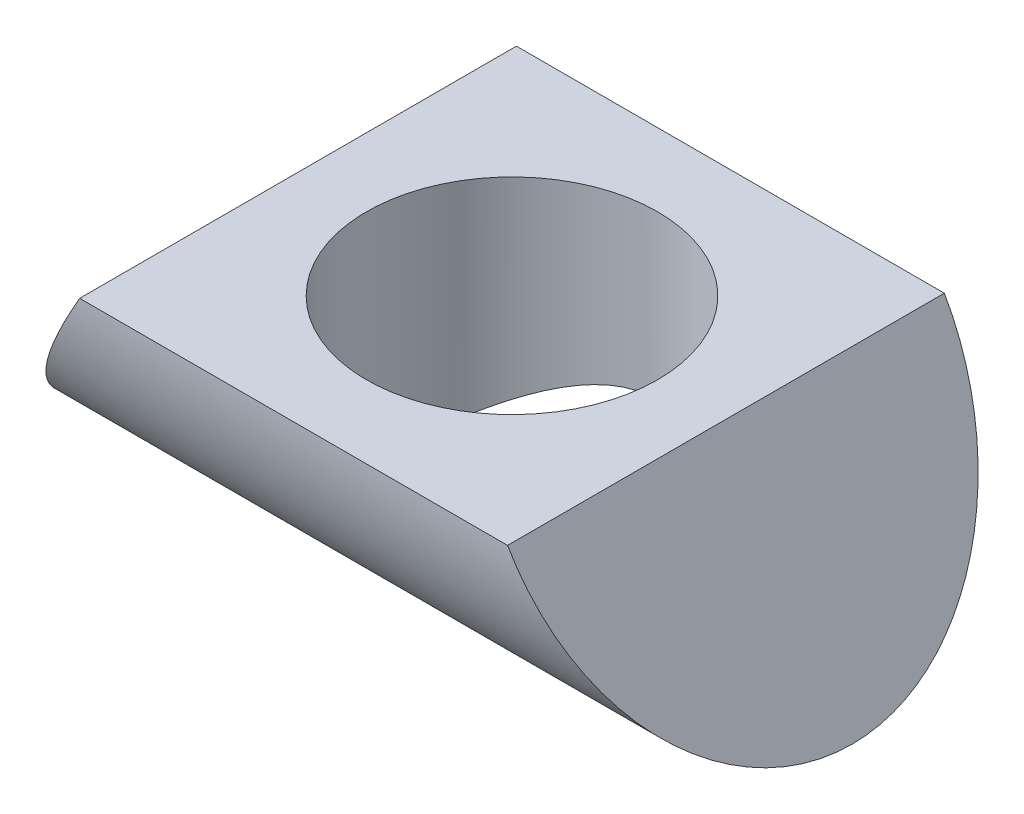
SolidWorks part; units mm, degrees
material "6061-T6 (SS)"
ref_plane "Front Plane" through (0, 0, 0) normal (0, 0, 1) x (1, 0, 0)
ref_plane "Top Plane" through (0, 0, 0) normal (0, 1, 0) x (1, 0, 0)
ref_plane "Right Plane" through (0, 0, 0) normal (1, 0, 0) x (0, 0, -1)
sketch "Sketch1" plane through (0, 0, 0) normal (0, 1, 0) x (1, 0, 0)
  line L0 (0, 20.354) -> (0, -20.728) construction
  line L1 (-20, 8) -> (20, 8) construction
  line L2 (-20, -8) -> (20, -8) construction
  circle A0 centre (-20, 0) radius 4.7625
  arc A1 (-20, 8) -> (-20, -8) centre (-20, 0) ccw construction
  circle A2 centre (20, 0) radius 4.7625
  arc A3 (20, 8) -> (20, -8) centre (20, 0) cw construction
  dimension "D1" = 9.525
  dimension "D2" = 20
  dimension "D3" = 16
sketch "Sketch2" plane through (0, 0, 0) normal (1, 0, 0) x (0, 0, -1)
  line L0 (-7.145, 0) -> (7.145, 0)
  arc A0 (-7.145, 0) -> (7.145, 0) centre (0, 0) ccw
  dimension "D1" = 14.29
extrude "Boss-Extrude3" add sketch "Sketch2" along normal blind 34 and the other way blind 34
extrude "Cut-Extrude1" cut sketch "Sketch1" against normal through all
sketch "Sketch3" plane through (0, 0, 0) normal (0, 1, 0) x (1, 0, 0)
  line L0 (0, 0) -> (0, 16.4803) construction
  line L1 (-20, 13) -> (20, 13)
  line L2 (-20, -13) -> (20, -13)
  arc A0 (-20, -13) -> (-20, 13) centre (-20, 0) cw
  arc A1 (20, -13) -> (20, 13) centre (20, 0) ccw
  dimension "D1" = 13
sketch "Sketch4" plane through (0, 0, 0) normal (0, 0, 1) x (1, 0, 0)
  line L0 (0, 0) -> (0, 13.4585) construction
  line L1 (-27, 0) -> (-20, 0) construction
  line L2 (-20, 0) -> (-13, 0) construction
  line L3 (13, 0) -> (20, 0) construction
  line L4 (-34, 0) -> (34, 0) construction
  line L5 (20, 0) -> (27, 0) construction
  line L34 (-43.2165, -4) -> (43.2165, -4) construction
  line L35 (20, 4.8152) -> (20, -11.8859) construction
  line L36 (-20, 4.8152) -> (-20, -11.8859) construction
  line L37 (-13, 0) -> (13, 0)
  line L38 (-7.8038, -9) -> (7.8038, -9)
  line L39 (32.1962, -9) -> (43.2165, -9)
  line L40 (43.2165, -9) -> (43.2165, 0)
  line L41 (43.2165, 0) -> (27, 0)
  line L42 (27, 0) -> (32.1962, -9)
  line L43 (13, 0) -> (7.8038, -9)
  line L44 (-43.2165, 0) -> (-27, 0)
  line L45 (-43.2165, -9) -> (-43.2165, 0)
  line L46 (-32.1962, -9) -> (-43.2165, -9)
  line L47 (-13, 0) -> (-7.8038, -9)
  line L48 (-27, 0) -> (-32.1962, -9)
  circle A0 centre (0, 9) radius 15 construction
  dimension "D1" = 30
  dimension "D2" = 9
  dimension "D4" = 60
  dimension "D5" = 60
  dimension "D6" = 20
  dimension "D7" = 20
  dimension "D8" = 7
  dimension "D11" = 60
  dimension "D12" = 60
  dimension "D13" = 9
extrude "Cut-Extrude3" cut sketch "Sketch4" against normal through all and the other way through all
sketch "Sketch5" plane through (0, 0, 0) normal (0, 1, 0) x (1, 0, 0)
  circle A0 centre (-20, 0) radius 7.25
  circle A1 centre (20, 0) radius 7.25
  dimension "D1" = 14.5
split line "Split Line1" [suppressed]
delete or keep bodies "Body-Delete1" type delete bodies bodies 112
